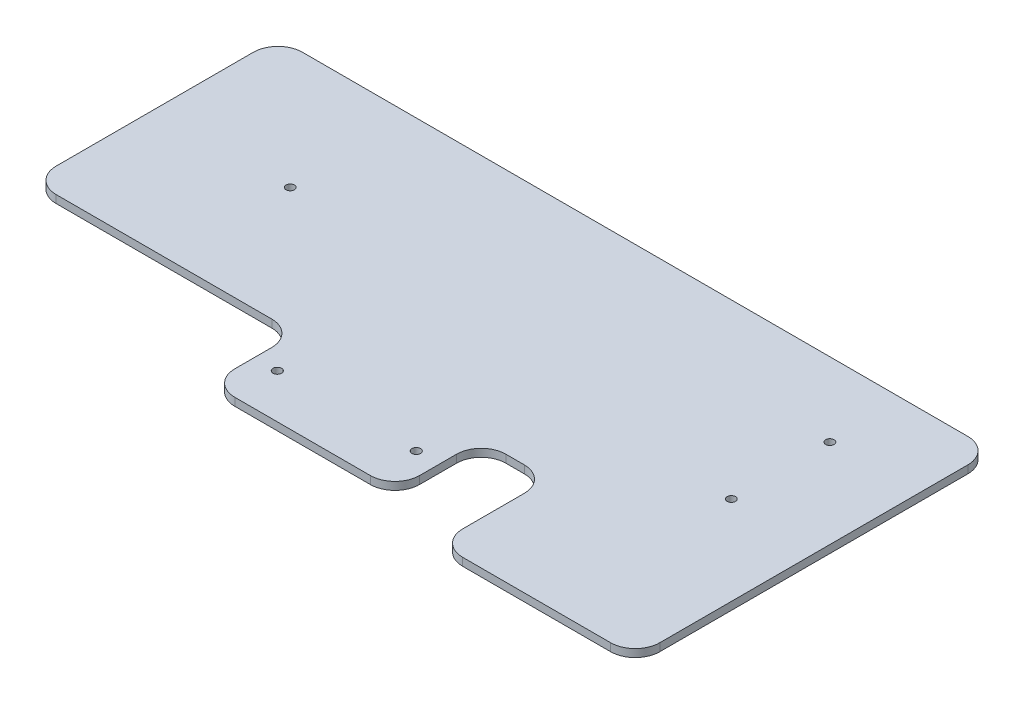
SolidWorks part; units mm, degrees
ref_plane "Front Plane" through (0, 0, 0) normal (0, 0, 1) x (1, 0, 0)
ref_plane "Top Plane" through (0, 0, 0) normal (0, 1, 0) x (1, 0, 0)
ref_plane "Right Plane" through (0, 0, 0) normal (1, 0, 0) x (0, 0, -1)
sketch "Sketch1" plane through (0, 0, 0) normal (0, 1, 0) x (1, 0, 0)
  line L0 (65, -50) -> (145, -50) construction
  line L1 (65, -50) -> (37.5, -50)
  line L2 (145, -50) -> (145, 50)
  line L3 (145, 50) -> (-145, 50)
  line L4 (-145, -50) -> (-145, 50)
  line L5 (145, -50) -> (-145, 50) construction
  line L6 (145, 50) -> (-145, -50) construction
  line L8 (145, -50) -> (145, -95)
  line L9 (145, -95) -> (65, -95)
  line L10 (65, -50) -> (65, -95)
  line L11 (-37.5, -50) -> (-145, -50)
  line L13 (-37.5, -50) -> (-37.5, -85)
  line L14 (-37.5, -85) -> (37.5, -85)
  line L15 (37.5, -50) -> (37.5, -85)
  line L16 (0, 85) -> (0, -85) construction
  circle A0 centre (28.194, -67.06) radius 1.75
  circle A1 centre (-28.194, -67.06) radius 1.75
  point P0 (0, 0)
  point P13 (0, -85)
  point P21 (0, 0)
  dimension "D8" = 3.5
  dimension "D1" = 290
  dimension "D2" = 100
  dimension "D3" = 45
  dimension "D4" = 80
  dimension "D5" = 75
  dimension "D6" = 35
  dimension "D7" = 17.94
  dimension "D9" = 9.306
extrude "Boss-Extrude1" add sketch "Sketch1" along normal blind 3.175
fillet "Fillet1" radius 10 10 edges at (145, 1.5875, -50) (145, 1.5875, 95) (65, 1.5875, 95) (65, 1.5875, 50) (-145, 1.5875, -50) (37.5, 1.5875, 85) (-37.5, 1.5875, 85) (-37.5, 1.5875, 50) (-145, 1.5875, 50) (37.5, 1.5875, 50)
sketch "Sketch2" plane through (0, 3.175, 0) normal (0, 1, 0) x (1, 0, 0)
  circle A0 centre (109, 20) radius 1.7 construction
  circle A1 centre (109, 20) radius 1.7 construction
  circle A2 centre (-90, 0) radius 1.7 construction
  circle A3 centre (109, -20) radius 1.7 construction
  circle A4 centre (-90, 0) radius 1.7 construction
  circle A5 centre (109, -20) radius 1.7 construction
  point P4 (109, 20)
  point P11 (-90, 0)
  point P12 (109, -20)
hole_wizard "standoff holes" positions "Sketch3" profile "Sketch4" hole size "M3" standard "ANSI Metric" end condition through all
sketch "Sketch3" plane through (0, 3.175, 0) normal (0, 1, 0) x (1, 0, 0)
  point P0 (-90, 0)
  point P3 (109, 20)
  point P6 (109, -20)
sketch "Sketch4" plane through (-90, 3.175, 0) normal (1, 0, 0) x (0, 0, 1)
  line L0 (0, 0) -> (0, 3.175)
  line L1 (0, 3.175) -> (1.7, 3.175)
  line L2 (1.7, 3.175) -> (1.7, 0)
  line L5 (1.7, 0) -> (0, 0)
  line L11 (0, -6.35) -> (0, 107.95) construction
  dimension "Thru Hole Dia." = 3.4
  dimension "Thru Hole Depth" = 3.175
